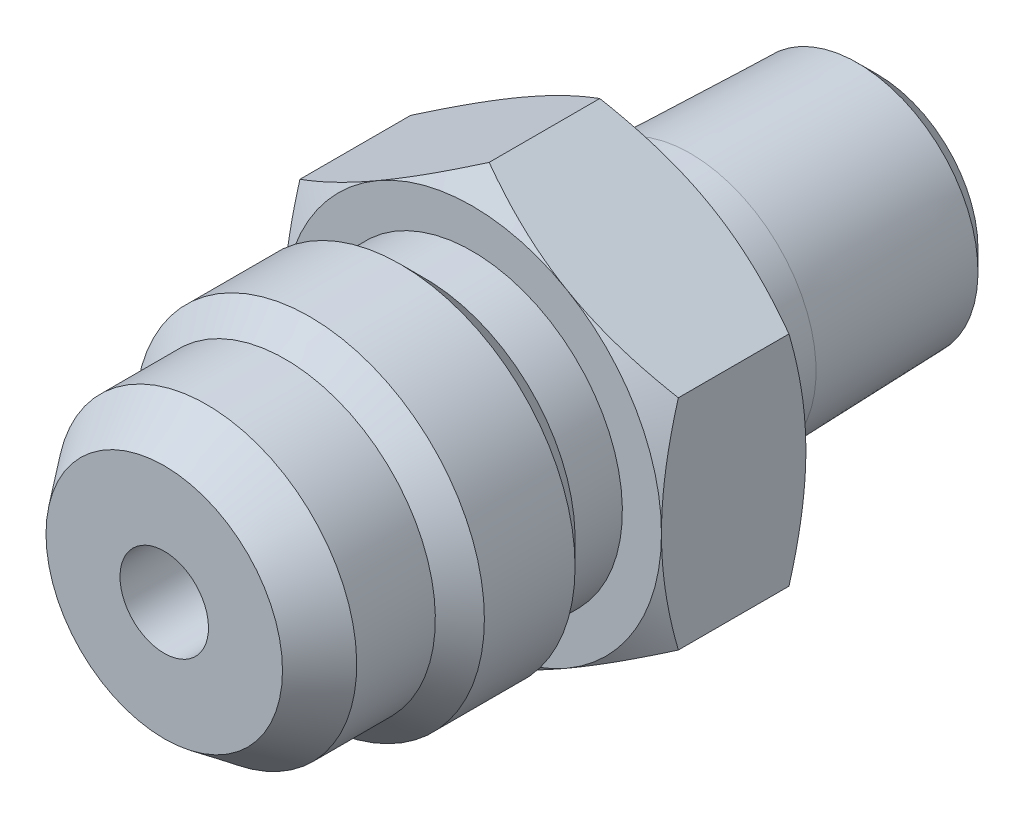
SolidWorks part; units mm, degrees
ref_plane "Front" through (0, 0, 0) normal (0, 0, 1) x (1, 0, 0)
ref_plane "Top" through (0, 0, 0) normal (0, 1, 0) x (1, 0, 0)
ref_plane "Right" through (0, 0, 0) normal (1, 0, 0) x (0, 0, -1)
sketch "Sketch1" plane through (0, 0, 0) normal (1, 0, 0) x (0, 0, -1)
  line L0 (-19.4469, 0) -> (19.4469, 0) construction
  line L1 (-19.4469, 2.413) -> (-19.4469, 6.4481)
  line L2 (-19.4469, 6.4481) -> (-17.1383, 8.1877)
  line L3 (-17.1383, 8.1877) -> (-12.8508, 8.1877)
  line L4 (-12.8508, 8.1877) -> (-11.5135, 9.525)
  line L5 (-11.5135, 9.525) -> (-6.5681, 9.525)
  line L6 (-6.5681, 9.525) -> (-5.2308, 8.1877)
  line L7 (-5.2308, 8.1877) -> (-2.6511, 8.1877)
  line L8 (-19.4469, 6.4481) -> (-18.7873, 6.4481) construction
  line L9 (-18.7873, 6.4481) -> (-18.1277, 6.4481) construction
  line L10 (-2.6511, 8.1877) -> (-2.6511, 10.3187)
  line L11 (-2.6511, 10.3187) -> (5.2229, 10.3187)
  line L12 (5.2229, 10.3187) -> (5.2229, 6.858)
  line L13 (5.2229, 6.858) -> (9.2412, 6.858)
  line L14 (9.2412, 6.858) -> (18.3545, 6.5743)
  line L15 (19.4469, 5.4819) -> (19.4469, 2.413)
  line L16 (19.4469, 2.413) -> (-19.4469, 2.413)
  line L17 (-17.1383, 8.1877) -> (-19.4469, 8.1877) construction
  line L18 (-19.4469, 8.1877) -> (-19.4469, 6.4481) construction
  line L19 (-11.5135, 9.525) -> (-12.8508, 9.525) construction
  line L20 (-12.8508, 9.525) -> (-12.8508, 8.1877) construction
  line L21 (-6.5681, 9.525) -> (-5.2308, 9.525) construction
  line L22 (-5.2308, 9.525) -> (-5.2308, 8.1877) construction
  line L23 (9.2412, 6.858) -> (19.4469, 6.858) construction
  line L24 (18.3545, 6.5743) -> (19.4469, 5.4819)
  line L25 (18.3545, 6.5743) -> (19.4469, 6.5402) construction
  line L26 (19.4469, 5.4819) -> (19.4469, 6.5402) construction
  line L27 (19.4469, 6.5402) -> (19.4469, 6.858) construction
  line L28 (19.4469, 6.5402) -> (19.976, 5.6237) construction
  line L29 (19.976, 5.6237) -> (20.1524, 5.6237) construction
  line L30 (20.1524, 5.6237) -> (20.7549, 6.6672) construction
  line L31 (20.7549, 6.6672) -> (19.3736, 6.6672) construction
  line L32 (19.3736, 6.6672) -> (19.4469, 6.5402) construction
  line L33 (19.7115, 6.082) -> (20.417, 6.082) construction
  line L34 (20.0642, 6.082) -> (20.0642, 5.6237) construction
  line L35 (20.0642, 5.8528) -> (21.4753, 5.8528) construction
  line L36 (-12.8508, 9.525) -> (-19.4469, 9.525) construction
  line L37 (-19.4469, 9.525) -> (-19.4469, 8.1877) construction
  line L38 (-19.4469, 9.525) -> (-20.0422, 8.4939) construction
  line L39 (-20.0422, 8.4939) -> (-20.2406, 8.4939) construction
  line L40 (-20.2406, 8.4939) -> (-20.9093, 9.652) construction
  line L41 (-20.9093, 9.652) -> (-19.3736, 9.652) construction
  line L42 (-19.3736, 9.652) -> (-19.4469, 9.525) construction
  line L43 (-19.7445, 9.0094) -> (-20.5383, 9.0094) construction
  line L44 (-20.1414, 9.0094) -> (-20.1414, 8.4939) construction
  line L45 (-20.1414, 8.7517) -> (-21.7289, 8.7517) construction
  line L46 (-18.1277, 6.4481) -> (-17.4681, 6.4481) construction
  line L47 (-17.4681, 6.4481) -> (-16.8085, 6.4481) construction
  line L48 (-16.8085, 6.4481) -> (-16.1488, 6.4481) construction
  line L49 (-16.1488, 6.4481) -> (-15.4892, 6.4481) construction
  line L50 (-15.4892, 6.4481) -> (-14.8296, 6.4481) construction
  line L51 (-14.8296, 6.4481) -> (-14.17, 6.4481) construction
  line L52 (-14.17, 6.4481) -> (-13.5104, 6.4481) construction
  line L53 (-13.5104, 6.4481) -> (-12.8508, 6.4481) construction
  line L54 (-12.8508, 8.1877) -> (-12.8508, 6.4481) construction
  line L55 (-17.1383, 8.1877) -> (-17.1383, 6.4481) construction
  dimension "D1" = 37
  dimension "D3" = 45
  dimension "D4" = 1.783
  dimension "D2" = 0.127
  dimension "D5" = 60
  dimension "D6" = 0.1764
  dimension "D7" = 0.7056
  dimension "D8" = 1.0583
  dimension "D9" = 0.127
  dimension "D10" = 60
  dimension "D11" = 0.1984
  dimension "D12" = 0.7937
  dimension "D13" = 2.5797
revolve "Revolve1" add sketch "Sketch1" angle 360 about L0
sketch "Sketch2" plane through (0, 0, 2.6511) normal (0, 0, 1) x (1, 0, 0)
  line L1 (0, 11.9151) -> (-10.3188, 5.9575)
  line L2 (-10.3188, 5.9575) -> (-10.3188, -5.9575)
  line L3 (-10.3188, -5.9575) -> (0, -11.9151)
  line L4 (0, -11.9151) -> (10.3188, -5.9575)
  line L5 (10.3188, -5.9575) -> (10.3188, 5.9575)
  line L6 (10.3188, 5.9575) -> (0, 11.9151)
  circle A0 centre (0, 0) radius 10.3187 construction
  circle A1 centre (0, 0) radius 10.3187 construction
  circle A2 centre (0, 0) radius 10.1917
  dimension "D1" = 0.127
extrude "Boss-Extrude1" add sketch "Sketch2" against normal up to surface (7.874 mm away) up to face at (0, -10.3187, -5.2229)
sketch "Sketch3" plane through (0, 0, 0) normal (1, 0, 0) x (0, 0, -1)
  line L0 (-19.4469, 0) -> (19.4469, 0) construction
  line L1 (1.2859, 10.3187) -> (1.2859, 0) construction
  line L2 (-2.6511, 10.3187) -> (5.2229, 10.3187) construction
  line L3 (-2.6511, 10.3187) -> (-2.6511, 11.9151)
  line L4 (-2.6511, 11.9151) -> (-1.7295, 11.9151)
  line L5 (5.2229, 11.9151) -> (-2.6511, 11.9151) construction
  line L6 (-1.7295, 11.9151) -> (-2.6511, 10.3187)
  line L7 (4.3012, 11.9151) -> (5.2229, 10.3187)
  line L8 (5.2229, 11.9151) -> (4.3012, 11.9151)
  line L9 (5.2229, 10.3187) -> (5.2229, 11.9151)
  dimension "D1" = 30
revolve "Cut-Revolve1" cut sketch "Sketch3" angle 360 about L0
sketch "Sketch4" plane through (0, 0, 19.4469) normal (0, 0, 1) x (1, 0, 0)
  circle A0 centre (0, 0) radius 9.525 construction
  circle A1 centre (0, 0) radius 9.525
curve "Helix/Spiral1" pitch 1.5875 height 16.7957 turns 10.58
sketch "Sketch5" [suppressed] plane through (0, 0, 0) normal (1, 0, 0) x (0, 0, -1)
  line L0 (-19.3736, 9.652) -> (-20.0422, 8.4939)
  line L1 (-20.0422, 8.4939) -> (-20.2406, 8.4939)
  line L2 (-20.2406, 8.4939) -> (-20.9093, 9.652)
  line L3 (-20.9093, 9.652) -> (-19.3736, 9.652)
sweep "Sweep1" [suppressed] add profiles "Sketch5" path "Helix/Spiral1"
sketch "Sketch6" [suppressed] plane through (0, 0, -19.4469) normal (0, 0, -1) x (-1, 0, 0)
  circle A0 centre (0, 0) radius 6.5402
curve "Helix/Spiral2" [suppressed]
sketch "Sketch7" [suppressed] plane through (0, 0, 0) normal (1, 0, 0) x (0, 0, -1)
  line L0 (19.3736, 6.6672) -> (19.976, 5.6237)
  line L1 (19.976, 5.6237) -> (20.1524, 5.6237)
  line L2 (20.1524, 5.6237) -> (20.7549, 6.6672)
  line L3 (20.7549, 6.6672) -> (19.3736, 6.6672)
sweep "Sweep2" [suppressed] add profiles "Sketch7" path "Helix/Spiral2"
sketch "Sketch8" [suppressed] plane through (0, 0, 0) normal (1, 0, 0) x (0, 0, -1)
  line L0 (-19.4469, 0) -> (19.4469, 0) construction
  line L1 (-5.2308, -11.9151) -> (9.2412, -11.9151)
  line L2 (-5.2308, -11.9151) -> (-5.2308, 11.9151)
  line L3 (-5.2308, 11.9151) -> (9.2412, 11.9151)
  line L4 (9.2412, -11.9151) -> (9.2412, 11.9151)
  line L5 (-5.2308, -11.9151) -> (9.2412, 11.9151) construction
  line L6 (-5.2308, 11.9151) -> (9.2412, -11.9151) construction
  line L7 (4.3012, 11.9151) -> (-1.7295, 11.9151) construction
  point P0 (2.0052, 0)
extrude "Cut-Extrude1" [suppressed] cut sketch "Sketch8" against normal through all both and the other way through all
combine bodies "Combine1" [suppressed] operation type subtract main body 111 bodies to subtract 114 115
other "CPoint1" parameters "Diameter"=12.7, "StubLength"=38.1
ref_axis "Axis1" through (0, 0, 29.4469) along (0, 0, -1)
equation "\"D6@Sketch1\"=\"ThreadPitch2@Sketch1\"*.125"
equation "\"D7@Sketch1\"=\"ThreadPitch2@Sketch1\"*.5"
equation "\"D8@Sketch1\"=\"ThreadPitch2@Sketch1\"*.75"
equation "\"D11@Sketch1\"=\"ThreadPitch1@Sketch1\"*.125"
equation "\"D12@Sketch1\"=\"ThreadPitch1@Sketch1\"*.5"
equation "\"D4@Helix/Spiral1\"=\"ThreadPitch1@Sketch1\""
equation "\"D3@Helix/Spiral1\"=\"Length@Sketch1\"-(\"HexWidth@Sketch1\"+\"SideLength2@Sketch1\")"
equation "\"D4@Helix/Spiral2\"=\"ThreadPitch2@Sketch1\""
equation "\"D3@Helix/Spiral2\"=\"ThreadFTE2@Sketch1\"+\"ThreadPitch2@Sketch1\""
equation "\"D13@Sketch1\"=\"ThreadPitch1@Sketch1\"*1.625"
